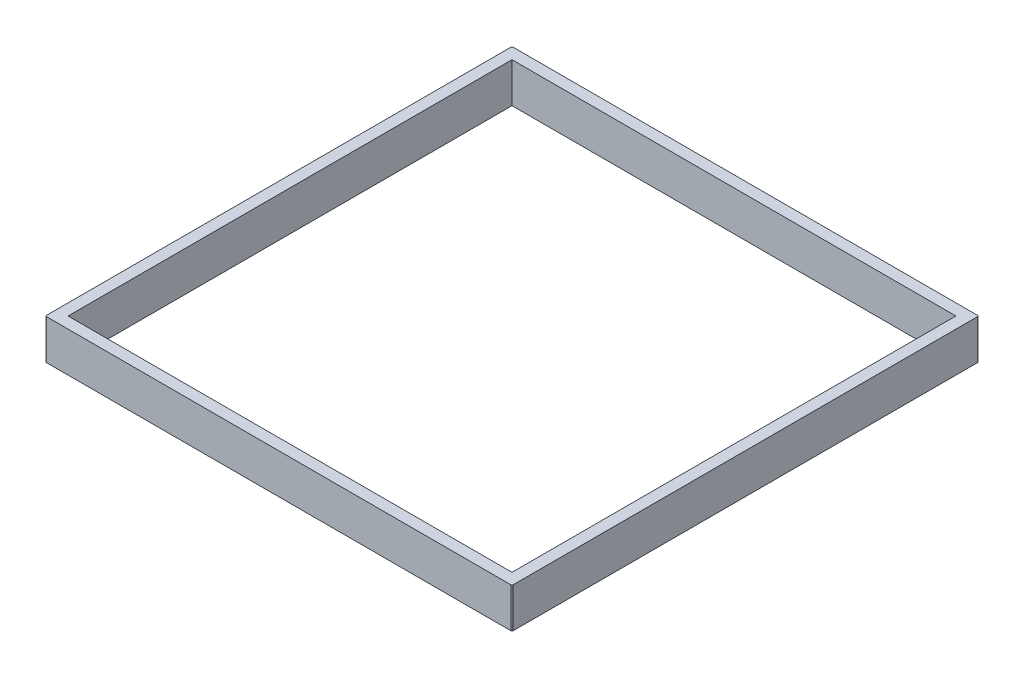
SolidWorks part; units mm, degrees
material "6061 Alloy"
ref_plane "Front Plane" through (0, 0, 0) normal (0, 0, 1) x (1, 0, 0)
ref_plane "Top Plane" through (0, 0, 0) normal (0, 1, 0) x (1, 0, 0)
ref_plane "Right Plane" through (0, 0, 0) normal (1, 0, 0) x (0, 0, -1)
sketch "Sketch1" plane through (0, 0, 0) normal (0, 1, 0) x (1, 0, 0)
  line L0 (2, -9) -> (80, -9)
  line L1 (0.2, -11) -> (81.8, -11)
  line L2 (0, -10.8) -> (0, 70.8)
  line L3 (0.2, 71) -> (81.8, 71)
  line L4 (82, -10.8) -> (82, 70.8)
  line L5 (80, -9) -> (80, 69)
  line L6 (2, 69) -> (80, 69)
  line L7 (2, -9) -> (2, 69)
  line L8 (0, 71) -> (82, 71) construction
  line L9 (82, -11) -> (82, 71) construction
  line L10 (0, -11) -> (82, -11) construction
  line L11 (0, -11) -> (0, 71) construction
  arc A0 (81.8, 71) -> (82, 70.8) centre (81.8, 70.8) cw
  arc A1 (81.8, -11) -> (82, -10.8) centre (81.8, -10.8) ccw
  arc A2 (0.2, -11) -> (0, -10.8) centre (0.2, -10.8) cw
  arc A3 (0, 70.8) -> (0.2, 71) centre (0.2, 70.8) cw
  dimension "D3" = 0.2
  dimension "D1" = 81.6
  dimension "D4" = 81.6
  dimension "D2" = 2
extrude "Coil" add sketch "Sketch1" along normal blind 7
sketch "Sketch9" [suppressed] plane through (0, 0, 0) normal (0, 1, 0) x (1, 0, 0)
  line L0 (2, 2) -> (78, 2)
  line L1 (0.2, 0) -> (79.8, 0)
  line L2 (0, 0.2) -> (0, 79.8)
  line L3 (0.2, 80) -> (79.8, 80)
  line L4 (80, 0.2) -> (80, 79.8)
  line L5 (78, 2) -> (78, 78)
  line L6 (2, 78) -> (78, 78)
  line L7 (2, 2) -> (2, 78)
  arc A0 (79.8, 80) -> (80, 79.8) centre (79.8, 79.8) cw
  arc A1 (79.8, 0) -> (80, 0.2) centre (79.8, 0.2) ccw
  arc A2 (0.2, 0) -> (0, 0.2) centre (0.2, 0.2) cw
  arc A3 (0, 79.8) -> (0.2, 80) centre (0.2, 79.8) cw
  arc A4 (78, 2) -> (78, 2) centre (78, 2) ccw
  arc A5 (78, 78) -> (78, 78) centre (78, 78) cw
  arc A6 (2, 78) -> (2, 78) centre (2, 78) cw
  arc A7 (2, 2) -> (2, 2) centre (2, 2) cw
  point P11 (0, 0)
  dimension "D1" = 0.2
  dimension "D3" = 79.6
  dimension "D4" = 79.6
  dimension "D2" = 2
extrude "Crazy Coil" [suppressed] add sketch "Sketch9" along normal blind 100
sketch "Sketch10" [suppressed] plane through (0, 0, 0) normal (-1, 0, 0) x (0, 0, 1)
  line L0 (0, 100) -> (0, 0) construction
  line L2 (-79.8, 100) -> (-0.2, 100) construction
  point P0 (-80, 100)
  point P1 (-80, 93)
  dimension "D1" = 80
  dimension "D2" = 7
sketch "Sketch11" [suppressed] plane through (80, 0, 0) normal (1, 0, 0) x (0, 0, -1)
  line L1 (0.2, 100) -> (79.8, 100) construction
  line L2 (80, 100) -> (80, 0) construction
  point P0 (0, 20)
  point P1 (0, 13)
  dimension "D1" = 7
  dimension "D2" = 80
  dimension "D3" = 80
ref_axis "Axis2" [suppressed] through (80, 20, 0) along (-0.5774, 0.5774, -0.5774)
ref_axis "Axis3" [suppressed] through (80, 13, 0) along (-0.5774, 0.5774, -0.5774)
ref_plane "Plane4" [suppressed] through (40, 0, -40) normal (0.7071, 0, -0.7071) x (-0.7071, 0, -0.7071)
ref_plane "Plane6" [suppressed] through (20, 40, 20) normal (-0.4082, -0.8165, -0.4082) x (0.9129, -0.3651, -0.1826)
ref_plane "Plane7" [suppressed] through (17.6667, 35.3333, 17.6667) normal (-0.4082, -0.8165, -0.4082) x (0.9129, -0.3651, -0.1826)
sketch "Sketch13" [suppressed] plane through (20, 40, 20) normal (-0.4082, -0.8165, -0.4082) x (0.9129, -0.3651, -0.1826)
  line L1 (-44.2949, 0) -> (92.4598, 0)
  line L2 (-44.2949, 0) -> (-44.2949, -126.3938)
  line L3 (-44.2949, -126.3938) -> (92.4598, -126.3938)
  line L4 (92.4598, 0) -> (92.4598, -126.3938)
extrude "Cut-Extrude1" [suppressed] cut sketch "Sketch13" against normal up to next
sketch "Sketch14" [suppressed] plane through (17.6667, 35.3333, 17.6667) normal (-0.4082, -0.8165, -0.4082) x (0.9129, -0.3651, -0.1826)
  line L1 (-34.7221, 5.4378) -> (92.1863, 5.4378)
  line L2 (-34.7221, 5.4378) -> (-34.7221, -123.3852)
  line L3 (-34.7221, -123.3852) -> (92.1863, -123.3852)
  line L4 (92.1863, 5.4378) -> (92.1863, -123.3852)
extrude "Cut-Extrude2" [suppressed] cut sketch "Sketch14" along normal up to next
equation "\"Wire Gauge\"=16"
equation "\"Wire Thickness\"=.127*(92^((36-\"Wire Gauge\")/39))"
equation "\"Dim1\"=\"Wire Thickness\"/8"
equation "\"Dim2\"=2*\"Dim1\""
equation "\"Dim3\"=2*\"Dim2\""
equation "\"Bend Radius\"=5 "
equation "\"Short Length\"=40-\"Dim3\""
equation "\"Long Length\"=\"Short Length\"*2"
